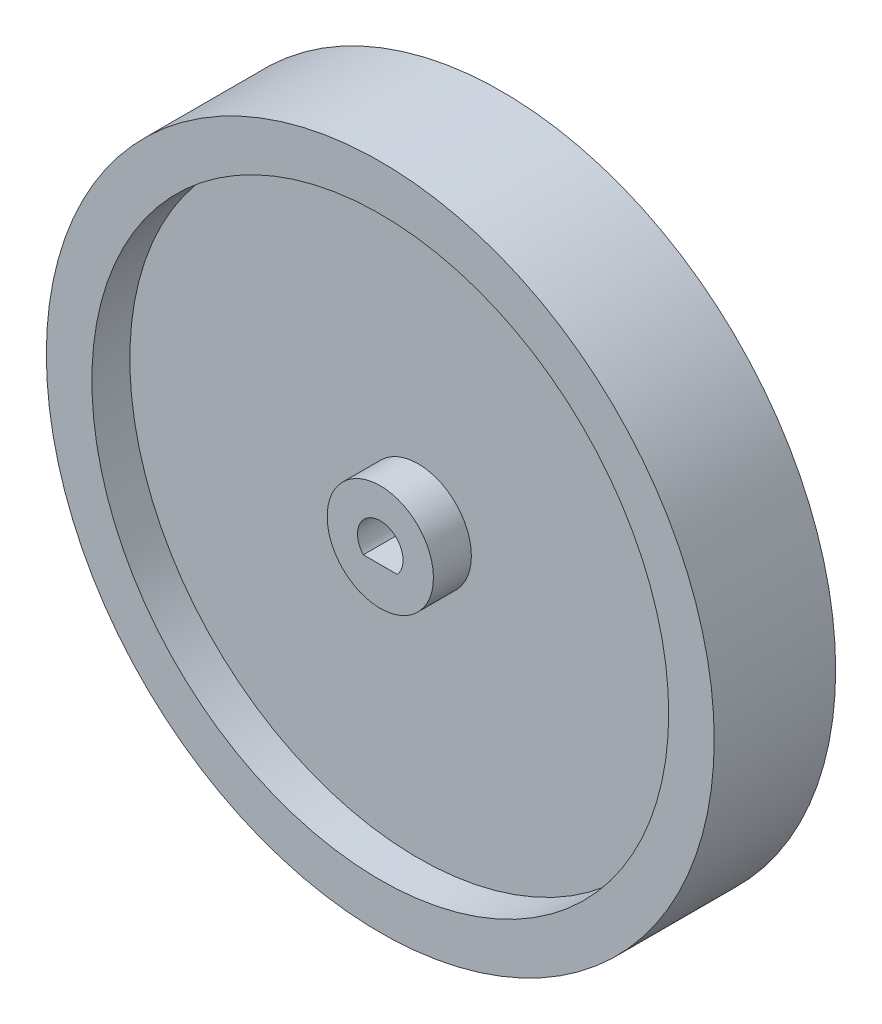
SolidWorks part; units mm, degrees
ref_plane "Front Plane" through (0, 0, 0) normal (0, 0, 1) x (1, 0, 0)
ref_plane "Top Plane" through (0, 0, 0) normal (0, 1, 0) x (1, 0, 0)
ref_plane "Right Plane" through (0, 0, 0) normal (1, 0, 0) x (0, 0, -1)
sketch "Sketch1" plane through (0, 0, 0) normal (0, 0, 1) x (1, 0, 0)
  line L0 (-1.118, -1) -> (1.118, -1)
  circle A0 centre (0, 0) radius 22
  circle A1 centre (0, 0) radius 19
  arc A2 (1.118, -1) -> (-1.118, -1) centre (0, 0) ccw
  circle A3 centre (0, 0) radius 3.5
  point P4 (0, 1.5)
  dimension "D1" = 44
  dimension "D2" = 3
  dimension "D4" = 1.5
  dimension "D5" = 2
  dimension "D3" = 2.5
extrude "Boss-Extrude1" add sketch "Sketch1" along normal blind 4 and the other way blind 4 contours A3 A2 L0 | A0 A1 region at (-21.3777, 0, 0) region at (-3.401, 0, 0)
extrude "Boss-Extrude2" add sketch "Sketch1<3>" along normal blind 1.5 and the other way blind 1.5 contours A1 A3 region at (-18.4626, 0, 0)
sketch "Sketch1<3>" plane through (0, 0, 0) normal (0, 0, 1) x (1, 0, 0) same geometry as "Sketch1"
